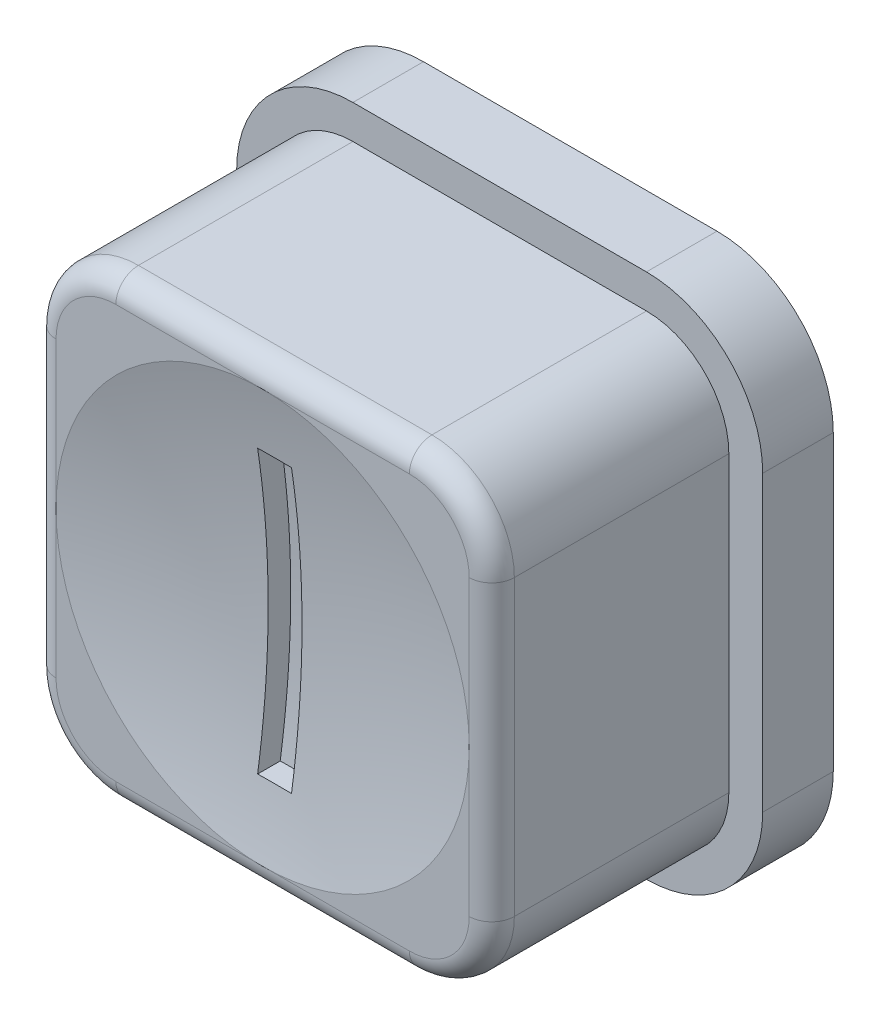
SolidWorks part; units mm, degrees
material "PET"
ref_plane "Front Plane" through (0, 0, 0) normal (0, 0, 1) x (1, 0, 0)
ref_plane "Top Plane" through (0, 0, 0) normal (0, 1, 0) x (1, 0, 0)
ref_plane "Right Plane" through (0, 0, 0) normal (1, 0, 0) x (0, 0, -1)
sketch "Sketch1" plane through (0, 0, 0) normal (0, 0, 1) x (1, 0, 0)
  line L0 (0, 0) -> (-5.1562, 0) construction
  line L4 (0, 5.1562) -> (0, -5.1562) construction
  line L8 (3.302, 5.1562) -> (-3.302, 5.1562)
  line L9 (-5.1562, 3.302) -> (-5.1562, -3.302)
  line L10 (-3.302, -5.1562) -> (3.302, -5.1562)
  line L11 (5.1562, -3.302) -> (5.1562, 3.302)
  arc A8 (-3.302, 5.1562) -> (-5.1562, 3.302) centre (-3.302, 3.302) ccw
  arc A9 (-5.1562, -3.302) -> (-3.302, -5.1562) centre (-3.302, -3.302) ccw
  arc A10 (3.302, -5.1562) -> (5.1562, -3.302) centre (3.302, -3.302) ccw
  arc A11 (5.1562, 3.302) -> (3.302, 5.1562) centre (3.302, 3.302) ccw
  point P6 (0, 0)
  dimension "D3" = 1.8542
  dimension "D4" = 10.3124
  dimension "D1" = 10.3124
  dimension "D5" = 10.3124
extrude "Boss-Extrude1" add sketch "Sketch1" against normal blind 5.334
fillet "Fillet1" radius 0.508 8 edges at (5.1562, 0, 0) (4.6131, -4.6131, 0) (0, -5.1562, 0) (-4.6131, -4.6131, 0) (-5.1562, 0, 0) (-4.6131, 4.6131, 0) (0, 5.1562, 0) (4.6131, 4.6131, 0)
sketch "Sketch2" plane through (0, 0, 0) normal (0, 0, 1) x (1, 0, 0)
  line L0 (0, 0) -> (0, -5.1562) construction
  line L1 (3.302, -5.1562) -> (-3.302, -5.1562) construction
  line L2 (0, 0) -> (5.1562, 0) construction
  line L3 (5.1562, 3.302) -> (5.1562, -3.302) construction
  circle A0 centre (0, 0) radius 4.572
  dimension "D1" = 9.144
extrude "Cut-Extrude1" [suppressed] cut sketch "Sketch2" against normal blind 0.254
sketch "Sketch3" [suppressed] plane through (0, 0, -0.254) normal (0, 0, 1) x (1, 0, 0)
  line L0 (0, -4.572) -> (0, 4.572) construction
  line L1 (-0.254, -4.572) -> (-0.254, 4.572)
  line L2 (0.254, -4.572) -> (0.254, 4.572)
  line L3 (0.254, -4.572) -> (0.254, 4.572)
  circle A0 centre (0, 0) radius 4.572 construction
  circle A1 centre (0, 0) radius 4.572 construction
  arc A2 (-0.254, -4.5649) -> (0.254, -4.5649) centre (0, 0) ccw
  arc A3 (0.254, 4.5649) -> (-0.254, 4.5649) centre (0, 0) ccw
  point P9 (0, 0)
  dimension "D2" = 0.254
  dimension "D1" = 0.254
extrude "Cut-Extrude2" [suppressed] cut sketch "Sketch3" against normal blind 0.127
sketch "Sketch4" plane through (0, 0, -5.334) normal (0, 0, -1) x (-1, 0, 0)
  line L8 (-5.9182, 3.302) -> (-5.9182, -3.302)
  line L9 (-3.302, -5.9182) -> (3.302, -5.9182)
  line L10 (5.9182, -3.302) -> (5.9182, 3.302)
  line L11 (3.302, 5.9182) -> (-3.302, 5.9182)
  line L12 (-5.9182, 3.302) -> (-5.9182, -3.302)
  line L13 (-3.302, -5.9182) -> (3.302, -5.9182)
  line L14 (5.9182, -3.302) -> (5.9182, 3.302)
  line L15 (3.302, 5.9182) -> (-3.302, 5.9182)
  arc A8 (-3.302, 5.9182) -> (-5.9182, 3.302) centre (-3.302, 3.302) ccw
  arc A9 (-5.9182, -3.302) -> (-3.302, -5.9182) centre (-3.302, -3.302) ccw
  arc A10 (3.302, -5.9182) -> (5.9182, -3.302) centre (3.302, -3.302) ccw
  arc A11 (5.9182, 3.302) -> (3.302, 5.9182) centre (3.302, 3.302) ccw
  arc A12 (-3.302, 5.9182) -> (-5.9182, 3.302) centre (-3.302, 3.302) ccw
  arc A13 (-5.9182, -3.302) -> (-3.302, -5.9182) centre (-3.302, -3.302) ccw
  arc A14 (3.302, -5.9182) -> (5.9182, -3.302) centre (3.302, -3.302) ccw
  arc A15 (5.9182, 3.302) -> (3.302, 5.9182) centre (3.302, 3.302) ccw
  dimension "D1" = 0.762
extrude "Boss-Extrude2" add sketch "Sketch4" along normal blind 1.5875
hole_wizard "#56 (0.0465) Diameter Hole1" positions "Sketch6" profile "Sketch7" hole size "#56" standard "ANSI Inch"
sketch "Sketch6" plane through (0, 0, -6.9215) normal (0, 0, -1) x (-1, 0, 0)
  point P0 (0, 0)
sketch "Sketch7" plane through (0, 0, -6.9215) normal (1, 0, 0) x (0, 1, 0)
  line L0 (0, 0) -> (0, 5.08)
  line L1 (0, 5.08) -> (0.5905, 5.08)
  line L2 (0.5905, 5.08) -> (0.5905, 0)
  line L5 (0.5905, 0) -> (0, 0)
  line L10 (0, 5.08) -> (-0.5906, 5.08) construction
  line L11 (0, -6.35) -> (0, 107.95) construction
  dimension "Hole Dia." = 1.1811
  dimension "Hole Depth" = 5.08
  dimension "Drill Angle" = 180
sketch "Sketch8" plane through (0, 0, 0) normal (1, 0, 0) x (0, 0, -1)
  line L0 (0, -3.302) -> (0, 3.302) construction
  line L1 (0.508, 0) -> (0, 0) construction
  line L2 (0, 4.6482) -> (0, 0)
  line L4 (0.508, 0) -> (0, 0)
  arc A0 (0, 4.6482) -> (0.508, 0) centre (-21.0115, 0) cw
  dimension "D1" = 0.508
revolve "Cut-Revolve1" cut sketch "Sketch8" angle 360 about L1
sketch "Sketch9" plane through (0, 0, 0) normal (0, 0, 1) x (1, 0, 0)
  line L1 (0.381, -3.175) -> (-0.381, -3.175)
  line L2 (0.381, -3.175) -> (0.381, 3.175)
  line L3 (0.381, 3.175) -> (-0.381, 3.175)
  line L4 (-0.381, -3.175) -> (-0.381, 3.175)
  line L5 (0.381, -3.175) -> (-0.381, 3.175) construction
  line L6 (0.381, 3.175) -> (-0.381, -3.175) construction
  point P0 (0, 0)
  dimension "D1" = 0.762
  dimension "D2" = 6.35
extrude "Cut-Extrude3" cut sketch "Sketch9" against normal blind 0.508 from surface starting at face at (0, 0, 0)
equation "\"D2@Sketch3\"=\"D1@Sketch3\""
